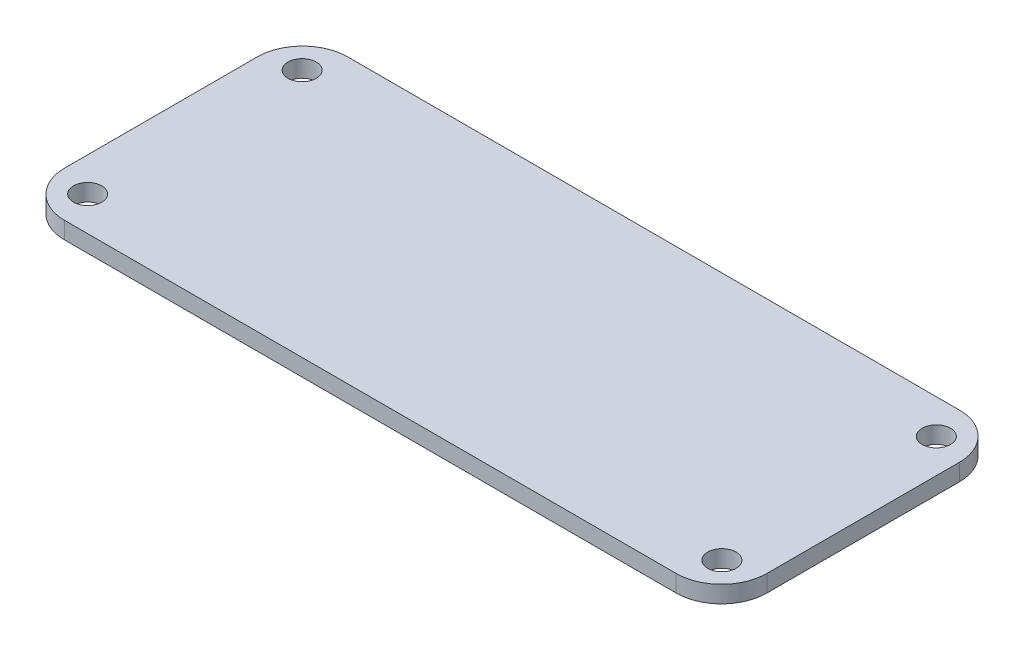
SolidWorks part; units mm, degrees
ref_plane "Alzado" through (0, 0, 0) normal (0, 0, 1) x (1, 0, 0)
ref_plane "Planta" through (0, 0, 0) normal (0, 1, 0) x (1, 0, 0)
ref_plane "Vista lateral" through (0, 0, 0) normal (1, 0, 0) x (0, 0, -1)
sketch "Croquis1" plane through (0, 0, 0) normal (0, 1, 0) x (1, 0, 0)
  line L1 (-31, 12.5) -> (31, 12.5)
  line L2 (-31, 12.5) -> (-31, -12.5)
  line L3 (-31, -12.5) -> (31, -12.5)
  line L4 (31, 12.5) -> (31, -12.5)
  line L5 (-31, 12.5) -> (31, -12.5) construction
  line L6 (-31, -12.5) -> (31, 12.5) construction
  point P0 (0, 0)
  dimension "D1" = 62
  dimension "D2" = 25
extrude "Saliente-Extruir1" add sketch "Croquis1" along normal blind 1.5
fillet "Redondeo1" radius 4 4 edges at (-31, 0.75, 12.5) (31, 0.75, 12.5) (31, 0.75, -12.5) (-31, 0.75, -12.5)
sketch "Croquis2" plane through (0, 1.5, 0) normal (0, 1, 0) x (1, 0, 0)
  line L1 (-28, 9.47) -> (28, 9.47) construction
  line L2 (-28, 9.47) -> (-28, -9.47) construction
  line L3 (-28, -9.47) -> (28, -9.47) construction
  line L4 (28, 9.47) -> (28, -9.47) construction
  line L5 (-28, 9.47) -> (28, -9.47) construction
  line L6 (-28, -9.47) -> (28, 9.47) construction
  circle A0 centre (-28, 9.47) radius 1.25
  circle A1 centre (28, 9.47) radius 1.25
  circle A2 centre (28, -9.47) radius 1.25
  circle A3 centre (-28, -9.47) radius 1.25
  point P0 (0, 0)
  dimension "D3" = 2.5
  dimension "D1" = 56
  dimension "D2" = 18.94
extrude "Cortar-Extruir1" cut sketch "Croquis2" against normal blind 10
